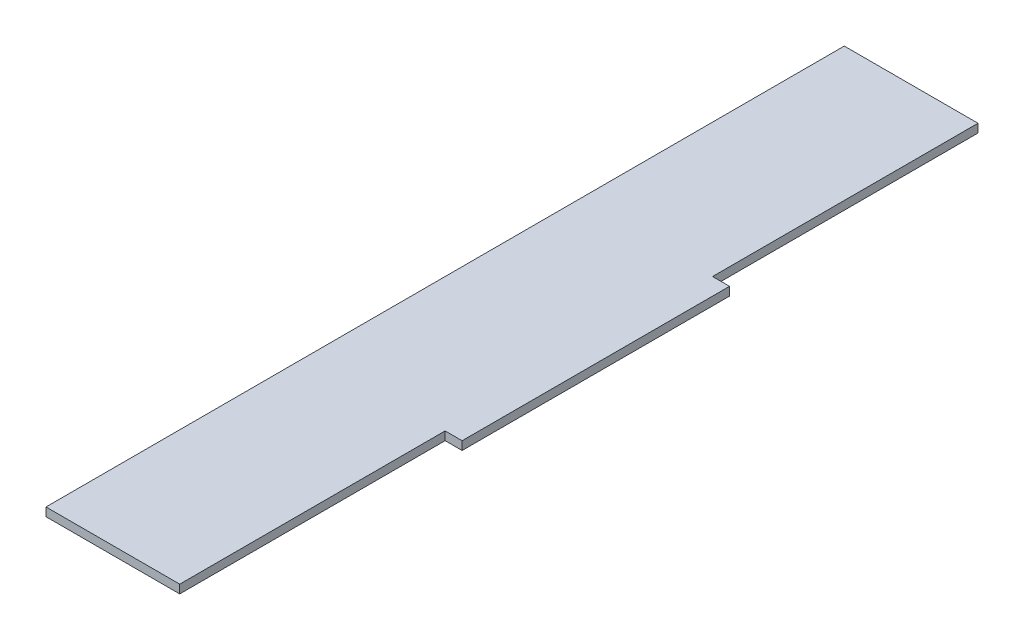
SolidWorks part; units mm, degrees
ref_plane "Front Plane" through (0, 0, 0) normal (0, 0, 1) x (1, 0, 0)
ref_plane "Top Plane" through (0, 0, 0) normal (0, 1, 0) x (1, 0, 0)
ref_plane "Right Plane" through (0, 0, 0) normal (1, 0, 0) x (0, 0, -1)
sketch "Sketch1" plane through (0, 0, 0) normal (0, 1, 0) x (1, 0, 0)
  line L0 (-25, 99.25) -> (25, 99.25)
  line L1 (25, 99.25) -> (25, 0)
  line L2 (25, 0) -> (31.35, 0)
  line L3 (31.35, 0) -> (31.35, -100)
  line L4 (31.35, -100) -> (25, -100)
  line L5 (25, -100) -> (25, -199.25)
  line L6 (25, -199.25) -> (-25, -199.25)
  line L7 (-25, -199.25) -> (-25, -100)
  line L8 (-25, -100) -> (-31.35, -100)
  line L9 (-31.35, -100) -> (-31.35, 0)
  line L10 (-31.35, 0) -> (-25, 0)
  line L11 (-25, 0) -> (-25, 99.25)
  line L12 (-25, 0) -> (-25, -100) construction
  point P11 (0, 99.25)
  point P14 (-31.35, -50)
  dimension "D1" = 6.35
  dimension "D2" = 100
  dimension "D3" = 50
  dimension "D4" = 298.5
extrude "Boss-Extrude1" add sketch "Sketch1" along normal blind 3.175 contours L11 L12 L7 L6 L5 L4 L3 L2 L1 L0 region at (1.1498, 0, 50)
equation "\"length\"= 298.5mm"
equation "\"w_mach\"= 50mm"
equation "\"w_tab\"= 100mm"
equation "\"t_wood\"= 0.125in"
equation "\"t_side\"= 0.25in"
equation "\"D1@Sketch1\"=\"t_side\""
equation "\"D2@Sketch1\"=\"w_tab\""
equation "\"D3@Sketch1\"=\"w_mach\""
equation "\"D4@Sketch1\"=\"length\""
equation "\"D1@Boss-Extrude1\"=\"t_wood\""
